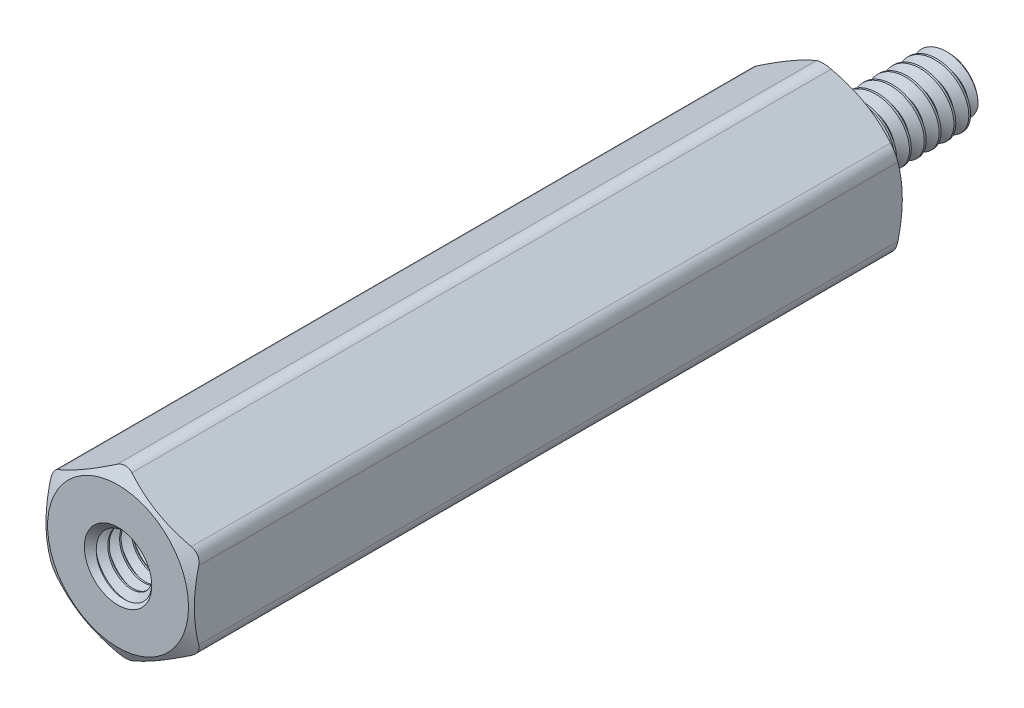
SolidWorks part; units mm, degrees
ref_plane "Front Plane" through (0, 0, 0) normal (0, 0, 1) x (1, 0, 0)
ref_plane "Top Plane" through (0, 0, 0) normal (0, 1, 0) x (1, 0, 0)
ref_plane "Right Plane" through (0, 0, 0) normal (1, 0, 0) x (0, 0, -1)
sketch "Sketch1" plane through (0, 0, 0) normal (0, 0, 1) x (1, 0, 0)
  line L1 (3.9688, 2.2914) -> (0, 4.5827)
  line L2 (0, 4.5827) -> (-3.9688, 2.2914)
  line L3 (-3.9688, 2.2914) -> (-3.9688, -2.2914)
  line L4 (-3.9688, -2.2914) -> (0, -4.5827)
  line L5 (0, -4.5827) -> (3.9688, -2.2914)
  line L6 (3.9688, -2.2914) -> (3.9688, 2.2914)
  circle A0 centre (0, 0) radius 3.9688 construction
  point P10 (0, -3.9688)
  dimension "Hex Size" = 7.9375
sketch "Sketch2" plane through (0, 0, 0) normal (1, 0, 0) x (0, 0, -1)
  line L0 (6.35, 0) -> (-38.1, 0) construction
  line L2 (0, 1.7526) -> (0, -1.7526) construction
  line L3 (-28.575, 1.7526) -> (-28.575, -1.7526) construction
  line L4 (-38.6953, 1.8213) -> (-38.3778, 1.2714) construction
  line L5 (-38.3778, 1.2714) -> (-38.0603, 1.8213) construction
  line L6 (-38.0603, 1.8213) -> (-38.6953, 1.8213) construction
  line L7 (-38.6556, 1.7526) -> (-38.1, 1.7526) construction
  line L8 (-38.4175, 1.3402) -> (-38.3381, 1.3402) construction
  line L9 (-38.3778, 1.3402) -> (-38.3778, 1.2714) construction
  line L10 (-38.3778, 1.7526) -> (-38.3778, 1.8213) construction
  line L11 (6.3004, 1.8385) -> (7.0941, 1.8385) construction
  line L12 (7.0941, 1.8385) -> (6.6973, 1.1511) construction
  line L13 (6.6973, 1.1511) -> (6.3004, 1.8385) construction
  line L14 (6.35, 1.7526) -> (7.0445, 1.7526) construction
  line L15 (6.6477, 1.237) -> (6.7469, 1.237) construction
  line L16 (6.6973, 1.237) -> (6.6973, 1.1511) construction
  line L17 (6.6973, 1.7526) -> (6.6973, 1.8385) construction
  line L18 (0, 4.5827) -> (-38.1, 4.5827) construction
  point P6 (0, 0)
  point P9 (-28.575, 0)
  dimension "Length" = 38.1
sketch "Sketch3" plane through (0, 0, 0) normal (1, 0, 0) x (0, 0, -1)
  line L0 (-28.575, 0) -> (6.35, 0)
  line L1 (-28.575, 1.7526) -> (-28.575, -1.7526) construction
  line L2 (6.35, 0) -> (6.35, 1.5542)
  line L3 (6.35, 1.5542) -> (6.1516, 1.7526)
  line L4 (6.1516, 1.7526) -> (1.0597, 1.7526)
  line L5 (1.0597, 1.7526) -> (0.762, 1.237)
  line L6 (-28.575, 0) -> (-28.575, 1.5542)
  line L7 (-28.575, 1.5542) -> (-28.7734, 1.7526)
  line L8 (-28.7734, 1.7526) -> (-37.9016, 1.7526)
  line L9 (-37.9016, 1.7526) -> (-38.1, 1.951)
  line L10 (6.1516, 0) -> (6.1516, -1.7526) construction
  line L11 (-38.1, 1.951) -> (-38.1, 3.9687)
  line L12 (-38.1, 3.9687) -> (0, 3.9687)
  line L14 (0.762, 1.237) -> (0.1984, 1.237)
  line L15 (0, 1.4355) -> (0, 3.9687)
  arc A0 (0, 1.4355) -> (0.1984, 1.237) centre (0.1984, 1.4355) ccw
  point P5 (-38.1, -3.9688)
  point P8 (-36.5125, -1.7526)
  point P9 (4.3656, -1.7526)
  point P27 (0, 1.237)
  dimension "D4" = 0.1984
  dimension "D2" = 0.1984
  dimension "D1" = 45
  dimension "D6" = 1.9844
  dimension "D7" = 60
  dimension "D3" = 1.5875
  dimension "D5" = 0.762
revolve "Revolve1" add sketch "Sketch3" angle 360 about L0
sketch "Sketch4" plane through (0, 0, 38.1) normal (0, 0, 1) x (1, 0, 0)
  line L0 (0, 3.9687) -> (0, 1.7526) construction
  line L1 (-3.9688, 2.2914) -> (-3.9688, -2.2914)
  line L2 (-3.9688, -2.2914) -> (0, -4.5827)
  line L3 (0, -4.5827) -> (3.9688, -2.2914)
  line L4 (3.9688, -2.2914) -> (3.9688, 2.2914)
  line L5 (3.9688, 2.2914) -> (0, 4.5827)
  line L6 (0, 4.5827) -> (-3.9688, 2.2914)
  circle A0 centre (0, 0) radius 3.9688 construction
  circle A1 centre (0, 0) radius 2.8607
  circle A2 centre (0, 0) radius 3.9688 construction
  point P16 (0, 2.8607)
extrude "Boss-Extrude1" add sketch "Sketch4" against normal up to surface (38.1 mm away) up to face at (0, 3.9687, 0)
sketch "Sketch5" plane through (0, 0, 38.1) normal (0, 0, 1) x (1, 0, 0)
  line L0 (-1.0053, 1.4356) -> (1.0053, -1.4356) construction
  line L1 (0, 1.7526) -> (0, -1.7526) construction
  line L3 (0, -2.9435) -> (0, 2.9435) construction
  circle A0 centre (0, 0) radius 3.7703
  point P11 (1.0053, -1.4356)
  dimension "D1" = 7.5406
  dimension "D2" = 35
extrude "Cut-Extrude1" cut sketch "Sketch5" against normal through all draft 60 flip side to cut
sketch "Sketch6" plane through (0, 0, 0) normal (0, 0, -1) x (-1, 0, 0)
  circle A0 centre (0, 0) radius 3.7703
  circle A1 centre (0, 0) radius 3.7703 construction
extrude "Cut-Extrude2" cut sketch "Sketch6" against normal through all draft 60 flip side to cut
fillet "Fillet1" radius 0.7937 6 edges at (0, 4.5827, 19.05) (-3.9688, -2.2914, 19.05) (0, -4.5827, 19.05) (3.9688, -2.2914, 19.05) (3.9688, 2.2914, 19.05) (-3.9688, 2.2914, 19.05)
sketch "Drawing1" plane through (0, 0, 0) normal (1, 0, 0) x (0, 0, -1)
  line L0 (-38.1, 1.7526) -> (-28.575, 1.7526) construction
  line L1 (-28.575, 1.7526) -> (-28.575, -1.7526) construction
  line L2 (-28.575, -1.7526) -> (-38.1, -1.7526) construction
sketch "Sketch7" plane through (0, 0, 0) normal (-1, 0, 0) x (0, 0, 1)
  line L0 (-6.6477, 1.237) -> (-6.7469, 1.237)
  line L1 (-6.7469, 1.237) -> (-7.0693, 1.7956)
  line L2 (-7.0941, 1.8385) -> (-6.6973, 1.1511) construction
  line L3 (-7.0693, 1.7956) -> (-6.3252, 1.7956)
  line L4 (-6.6973, 1.1511) -> (-6.3004, 1.8385) construction
  line L5 (-6.3252, 1.7956) -> (-6.6477, 1.237)
  line L6 (-6.6973, 1.7526) -> (-6.6973, 1.8385) construction
  point P12 (-6.6973, 1.7956)
sketch "Sketch8" plane through (0, 0, -6.35) normal (0, 0, -1) x (-1, 0, 0)
  circle A0 centre (0, 0) radius 1.7526
curve "Helix/Spiral1" pitch 0.7937 height 6.1595 turns 7.76
sweep "Cut-Sweep1" cut profiles "Sketch7" path "Helix/Spiral1" align with end faces yes
sketch "Sketch9" plane through (0, 0, 28.575) normal (0, 0, 1) x (1, 0, 0)
  circle A0 centre (0, 0) radius 1.951
extrude "Boss-Extrude2" add sketch "Sketch9" along normal up to surface (9.525 mm away)
sketch "Sketch10" plane through (0, 0, 0) normal (1, 0, 0) x (0, 0, -1)
  line L0 (6.35, 0) -> (-38.1, 0) construction
  line L1 (-28.575, 1.7526) -> (-38.1, 1.7526)
  line L2 (-28.575, 1.7526) -> (-28.575, 0)
  line L3 (-28.575, 0) -> (-38.1, 0)
  line L4 (-38.1, 1.7526) -> (-38.1, 0)
revolve "Revolve2" add sketch "Sketch10" angle 360 about L0
sketch "Sketch11" plane through (0, 0, 38.1) normal (0, 0, 1) x (1, 0, 0)
  circle A0 centre (0, 0) radius 1.7526
  circle A1 centre (0, 0) radius 1.7526 construction
sketch "Sketch12" plane through (0, 0, 0) normal (1, 0, 0) x (0, 0, -1)
  line L0 (-38.4175, 1.3402) -> (-38.3381, 1.3402)
  line L1 (-38.3381, 1.3402) -> (-38.0802, 1.787)
  line L2 (-38.3778, 1.2714) -> (-38.0603, 1.8213) construction
  line L3 (-38.0802, 1.787) -> (-38.6755, 1.787)
  line L4 (-38.6953, 1.8213) -> (-38.3778, 1.2714) construction
  line L5 (-38.6755, 1.787) -> (-38.4175, 1.3402)
  line L6 (-38.3778, 1.7526) -> (-38.3778, 1.8213) construction
  point P12 (-38.3778, 1.787)
curve "Helix/Spiral2" pitch 0.635 height 10.16 turns 16
sweep "Cut-Sweep2" cut profiles "Sketch12" path "Helix/Spiral2" align with end faces yes
combine bodies "Combine1" operation type subtract main body 113 bodies to subtract 114
sketch "Sketch13" plane through (0, 0, 38.1) normal (0, 0, 1) x (1, 0, 0)
  circle A0 centre (0, 0) radius 1.8034
  dimension "D1" = 0.0508
extrude "Cut-Extrude3" cut sketch "Sketch13" against normal blind 0.9525 draft 45.118
equation "\"Thread Pitch (B)/8@Sketch2\" = \"Thread Pitch (B)@Sketch2\" / 8"
equation "\"Thread Pitch (A)/8@Sketch2\" = \"Thread Pitch (A)@Sketch2\" / 8"
equation "\"D1@Sketch5\" = \"Hex Size@Sketch1\" * .95"
equation "\"D1@Fillet1\" = \"Hex Size@Sketch1\" * .1"
equation "\"D2@Sketch3\" = \"Thread Pitch (A)@Sketch2\" * .25"
equation "\"D4@Sketch3\" = \"D2@Sketch3\""
equation "\"D6@Sketch3\" = \"Thread Pitch (A)@Sketch2\" * 2.5"
equation "\"D3@Helix/Spiral1\" = \"Thread Length (A)@Sketch2\" - \"D5@Sketch3\" * .25"
equation "\"D4@Helix/Spiral1\" = \"Thread Pitch (A)@Sketch2\""
equation "\"D3@Sketch3\" = \"Thread Pitch (B)@Sketch2\" * 2.5"
equation "\"D5@Sketch3\" = \"Thread Length (A)@Sketch2\" * .12"
equation "\"D3@Helix/Spiral2\" = \"Minimum Thread Length (B)@Sketch2\" + \"Thread Pitch (B)@Sketch2\""
equation "\"D4@Helix/Spiral2\" = \"Thread Pitch (B)@Sketch2\""
equation "\"Pitch Natural Taper Angle\"= ATN ( \"Thread Pitch (B)@Sketch2\" / 2 )"
equation "\"Angle Count\"= 45 / \"Pitch Natural Taper Angle\""
equation "\"Rounded Angle Count\"= ROUND ( \"Angle Count\" )"
equation "\"Taper Angle\"= \"Rounded Angle Count\" * \"Pitch Natural Taper Angle\""
equation "\"D1@Cut-Extrude3\"=\"Thread Pitch (B)@Sketch2\"*1.5"
equation "\"D3@Cut-Extrude3\"=\"Taper Angle\""
